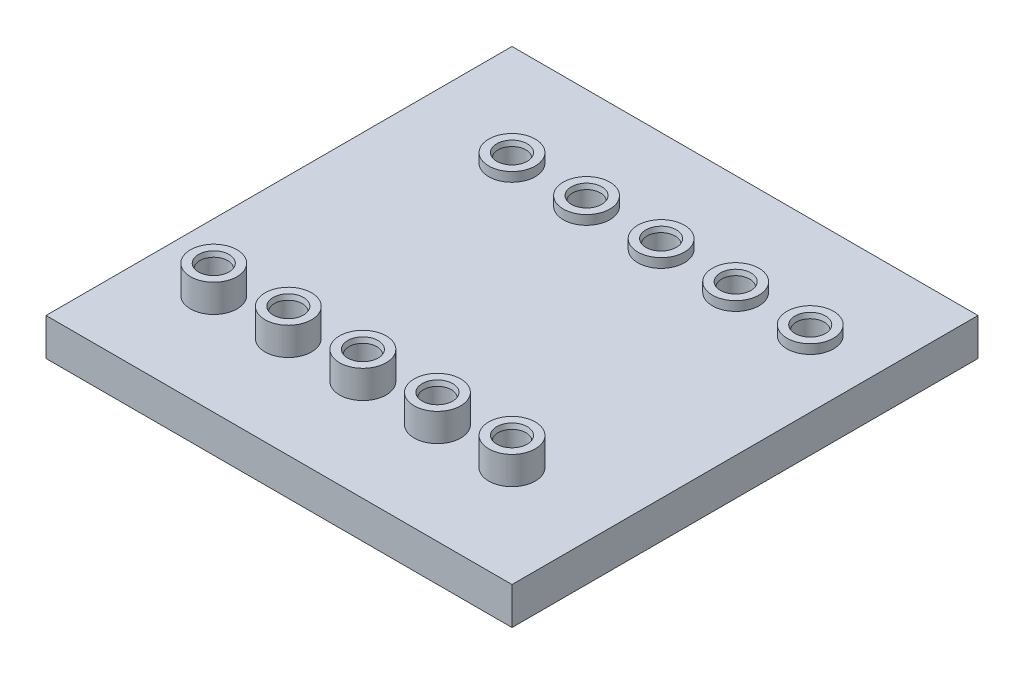
SolidWorks part; units mm, degrees
ref_plane "Front Plane" through (0, 0, 0) normal (0, 0, 1) x (1, 0, 0)
ref_plane "Top Plane" through (0, 0, 0) normal (0, 1, 0) x (1, 0, 0)
ref_plane "Right Plane" through (0, 0, 0) normal (1, 0, 0) x (0, 0, -1)
sketch "Sketch1" plane through (0, 0, 0) normal (0, 1, 0) x (1, 0, 0)
  line L0 (-14.1421, 14.1421) -> (25, 14.1421) construction
  line L1 (-25, -25) -> (25, -25)
  line L2 (-25, -25) -> (-25, 25)
  line L3 (-25, 25) -> (25, 25)
  line L4 (25, -25) -> (25, 25)
  line L5 (-25, -25) -> (25, 25) construction
  line L6 (-25, 25) -> (25, -25) construction
  line L7 (14.1421, -14.1421) -> (-25, -14.1421) construction
  circle A0 centre (-14.1421, 14.1421) radius 2.5
  circle A1 centre (14.1421, -14.1421) radius 2.5
  circle A2 centre (-6.1421, 14.1421) radius 2.5
  circle A3 centre (9.8579, 14.1421) radius 2.5
  circle A4 centre (17.8579, 14.1421) radius 2.5
  circle A5 centre (1.8579, 14.1421) radius 2.5
  circle A6 centre (6.1421, -14.1421) radius 2.5
  circle A7 centre (-1.8579, -14.1421) radius 2.5
  circle A8 centre (-9.8579, -14.1421) radius 2.5
  circle A9 centre (-17.8579, -14.1421) radius 2.5
  point P0 (0, 0)
  dimension "D2" = 5
  dimension "D1" = 50
  dimension "D3" = 20
  dimension "D4" = 20
  dimension "D5" = 8
  dimension "D6" = 8
  dimension "D7" = 8
  dimension "D8" = 8
  dimension "D9" = 8
  dimension "D10" = 8
  dimension "D11" = 8
  dimension "D12" = 8
extrude "Boss-Extrude2" add sketch "Sketch1" along normal blind 4 contours L1 L4 L3 L2
extrude "Boss-Extrude3" add sketch "Sketch1<4>" along normal blind 1 from surface contours A0 | A2 | A5 | A3 | A4 starting at face at (0, 4, 0)
sketch "Sketch1<4>" plane through (0, 0, 0) normal (0, 1, 0) x (1, 0, 0) same geometry as "Sketch1"
extrude "Boss-Extrude4" add sketch "Sketch1<5>" along normal blind 3 from surface contours A1 | A9 | A8 | A7 | A6 starting at face at (17.8579, 4, -16.6421)
sketch "Sketch1<5>" plane through (0, 0, 0) normal (0, 1, 0) x (1, 0, 0) same geometry as "Sketch1"
hole_wizard "CSK for M2 Flat Head Machine Screw1" positions "Sketch4" profile "Sketch3" countersink size "M2" standard "ANSI Metric"
sketch "Sketch4" plane through (0, 5, 0) normal (0, 1, 0) x (1, 0, 0)
  point P0 (-14.1421, 14.1421)
  point P4 (-6.1421, 14.1421)
  point P7 (1.8579, 14.1421)
  point P10 (9.8579, 14.1421)
  point P13 (17.8579, 14.1421)
sketch "Sketch3" plane through (-14.1421, 5, -14.1421) normal (1, 0, 0) x (0, 0, 1)
  line L0 (0, 0) -> (0, 3.5)
  line L1 (0, 3.5) -> (1.5, 3.5)
  line L2 (1.5, 3.5) -> (1.5, 0.5038)
  line L3 (1.5, 0.5038) -> (1.635, 0)
  line L5 (1.635, 0) -> (0, 0)
  line L6 (-1.5, 0.5038) -> (-1.635, 0) construction
  line L10 (0, 3.5) -> (-1.5, 3.5) construction
  line L11 (0, -6.35) -> (0, 107.95) construction
  dimension "Hole Dia." = 3
  dimension "Hole Depth" = 3.5
  dimension "Near C'Sink Dia." = 3.27
  dimension "Near C'Sink Angle" = 30
  dimension "Drill Angle" = 180
hole_wizard "CSK for M2 Flat Head Machine Screw2" positions "Sketch6" profile "Sketch5" countersink size "M2" standard "ANSI Metric"
sketch "Sketch6" plane through (0, 7, 0) normal (0, 1, 0) x (1, 0, 0)
  point P0 (14.1421, -14.1421)
  point P4 (-17.8579, -14.1421)
  point P7 (-9.8579, -14.1421)
  point P10 (-1.8579, -14.1421)
  point P13 (6.1421, -14.1421)
sketch "Sketch5" plane through (14.1421, 7, 14.1421) normal (1, 0, 0) x (0, 0, 1)
  line L0 (0, 0) -> (0, 6)
  line L1 (0, 6) -> (1.5, 6)
  line L2 (1.5, 6) -> (1.5, 0.5038)
  line L3 (1.5, 0.5038) -> (1.635, 0)
  line L5 (1.635, 0) -> (0, 0)
  line L6 (-1.5, 0.5038) -> (-1.635, 0) construction
  line L10 (0, 6) -> (-1.5, 6) construction
  line L11 (0, -6.35) -> (0, 107.95) construction
  dimension "Hole Dia." = 3
  dimension "Hole Depth" = 6
  dimension "Near C'Sink Dia." = 3.27
  dimension "Near C'Sink Angle" = 30
  dimension "Drill Angle" = 180
